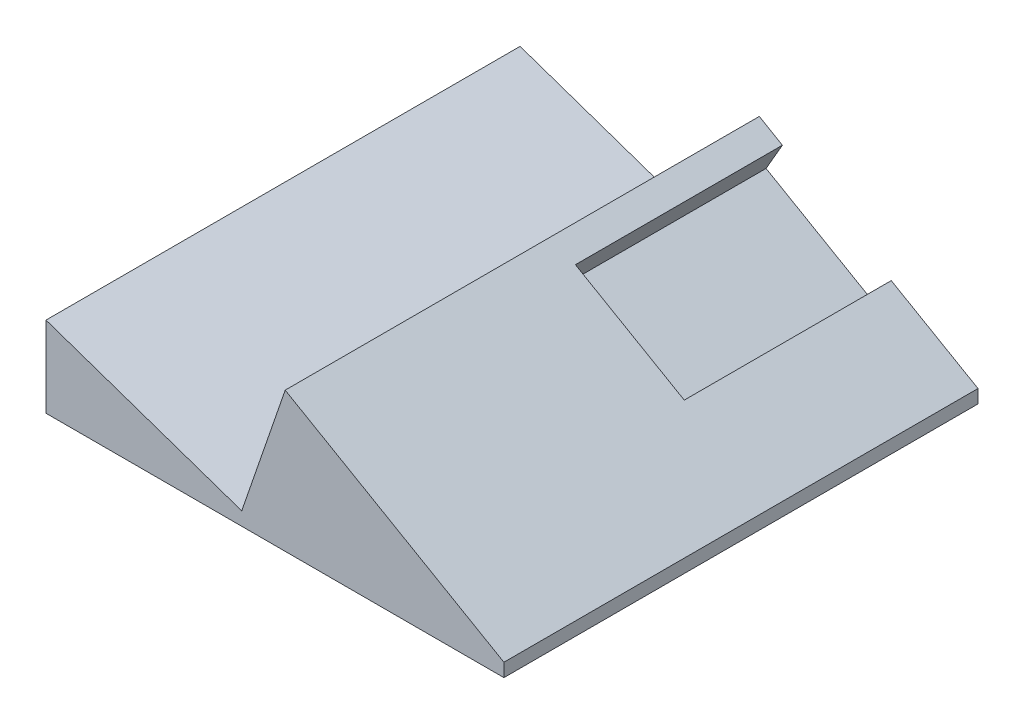
SolidWorks part; units mm, degrees
ref_plane "Front Plane" through (0, 0, 0) normal (0, 0, 1) x (1, 0, 0)
ref_plane "Top Plane" through (0, 0, 0) normal (0, 1, 0) x (1, 0, 0)
ref_plane "Right Plane" through (0, 0, 0) normal (1, 0, 0) x (0, 0, -1)
sketch "Sketch1" plane through (0, 0, 0) normal (0, 1, 0) x (1, 0, 0)
  line L1 (15, -51.5) -> (-15, -51.5)
  line L2 (15, -51.5) -> (15, 51.5)
  line L3 (15, 51.5) -> (-15, 51.5)
  line L4 (-15, -51.5) -> (-15, 51.5)
  line L5 (15, -51.5) -> (-15, 51.5) construction
  line L6 (15, 51.5) -> (-15, -51.5) construction
  point P0 (0, 0)
  dimension "D1" = 103
  dimension "D2" = 30
extrude "Boss-Extrude1" add sketch "Sketch1" along normal blind 2
sketch "Sketch2" plane through (0, 0, 51.5) normal (0, 0, 1) x (1, 0, 0)
  line L0 (15, 2) -> (-35.2295, 31)
  line L1 (0, 2) -> (0, 0)
  line L2 (0, 0) -> (18.4641, 0)
  line L3 (15, 2) -> (18.4641, 0)
  line L8 (-53.5765, 12.0888) -> (-47.0676, 31) construction
  line L9 (-47.0676, 31) -> (-17.7552, 20.9112)
  line L10 (-17.7552, 20.9112) -> (-24.2641, 2) construction
  line L11 (-24.2641, 2) -> (-53.5765, 12.0888)
  line L12 (-15, 2) -> (15, 2) construction
  line L13 (-53.5765, 12.0888) -> (-53.5765, 0)
  line L14 (-24.2641, 2) -> (-49.8195, 2) construction
  line L17 (-15, 2) -> (-15, 0)
  line L18 (-53.5765, 0) -> (-15, 0)
  line L19 (-15, 2) -> (0, 2)
  line L20 (-56.2053, 2) -> (-56.2053, 31) construction
  line L21 (-17.7552, 20.9112) -> (-24.2641, 2)
  line L22 (-56.2053, 31) -> (-14.2536, 31) construction
  line M19 (15, 2) -> (-15, 2)
  line M20 (-15, 2) -> (-15, 0)
  dimension "D1" = 30
  dimension "D2" = 20
  dimension "D3" = 31
  dimension "D4" = 29
extrude "Boss-Extrude2" add sketch "Sketch2" against normal blind 103 contours L21 L11 L0 M20 M19 region at (-20.907, 6.6295, 51.5)
sketch "Sketch6" plane through (4.616, 7.9952, 0) normal (0.5, 0.866, 0) x (0.866, -0.5, 0)
  line L0 (-21.8321, -11.5) -> (-21.8321, 58.5)
  line L1 (-21.8321, 58.5) -> (-3.0096, 58.5)
  line L2 (-3.0096, 58.5) -> (-3.0096, -11.5)
  line L3 (-3.0096, -11.5) -> (-21.8321, -11.5)
  line L4 (11.9904, -51.5) -> (-25.8321, -51.5) construction
  line L5 (-25.8321, 51.5) -> (-25.8321, -51.5) construction
  line L6 (11.9904, -51.5) -> (11.9904, 51.5) construction
  dimension "D1" = 70
  dimension "D2" = 40
  dimension "D3" = 4
  dimension "D4" = 15
extrude "Cut-Extrude3" cut sketch "Sketch6" against normal blind 4.8964
sketch "Sketch7" plane through (-53.5765, 0, 0) normal (-1, 0, 0) x (0, 0, 1)
  line L0 (-51.5, 20.9112) -> (51.5, 20.9112) construction
  line L1 (-51.5, 0) -> (-19.5, 0)
  line L2 (-51.5, 0) -> (-51.5, 20.9112)
  line L3 (-51.5, 20.9112) -> (-19.5, 20.9112)
  line L4 (-19.5, 0) -> (-19.5, 20.9112)
  line L5 (51.5, 12.0888) -> (51.5, 0) construction
  dimension "D1" = 71
extrude "Cut-Extrude4" cut sketch "Sketch7" against normal blind 73 contours L2 L1 L4 L3
